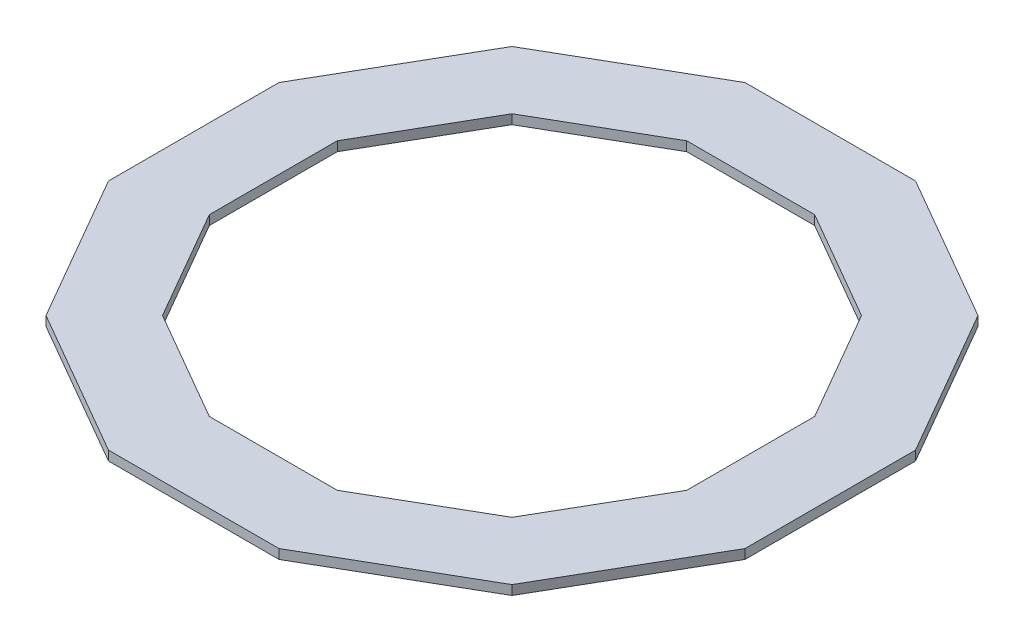
SolidWorks part; units mm, degrees
material "ABS PC"
ref_plane "Front Plane" through (0, 0, 0) normal (0, 0, 1) x (1, 0, 0)
ref_plane "Top Plane" through (0, 0, 0) normal (0, 1, 0) x (1, 0, 0)
ref_plane "Right Plane" through (0, 0, 0) normal (1, 0, 0) x (0, 0, -1)
sketch "Sketch1" plane through (0, 0, 0) normal (0, 1, 0) x (1, 0, 0)
  line L0 (26.296, 98.1381) -> (-26.296, 98.1381)
  line L1 (-26.296, 98.1381) -> (-71.842, 71.842)
  line L2 (-71.842, 71.842) -> (-98.1381, 26.296)
  line L3 (-98.1381, 26.296) -> (-98.1381, -26.296)
  line L4 (-98.1381, -26.296) -> (-71.842, -71.842)
  line L5 (-71.842, -71.842) -> (-26.296, -98.1381)
  line L6 (-26.296, -98.1381) -> (26.296, -98.1381)
  line L7 (26.296, -98.1381) -> (71.842, -71.842)
  line L8 (71.842, -71.842) -> (98.1381, -26.296)
  line L9 (98.1381, -26.296) -> (98.1381, 26.296)
  line L10 (98.1381, 26.296) -> (71.842, 71.842)
  line L11 (71.842, 71.842) -> (26.296, 98.1381)
  circle A0 centre (0, 0) radius 101.6
  dimension "D1" = 203.2
extrude "Boss-Extrude1" add sketch "Sketch1" against normal blind 2.921 contours L10 L11 L0 L1 L2 L3 L4 L5 L6 L7 L8 L9 region at (0, 0, 0)
sketch "Sketch3" plane through (0, 0, 0) normal (0, 1, 0) x (1, 0, 0)
  line L12 (-53.8815, 53.8815) -> (-19.722, 73.6035)
  line L13 (-19.722, 73.6035) -> (19.722, 73.6035)
  line L14 (19.722, 73.6035) -> (53.8815, 53.8815)
  line L15 (53.8815, 53.8815) -> (73.6035, 19.722)
  line L16 (73.6035, 19.722) -> (73.6035, -19.722)
  line L17 (73.6035, -19.722) -> (53.8815, -53.8815)
  line L18 (53.8815, -53.8815) -> (19.722, -73.6035)
  line L19 (19.722, -73.6035) -> (-19.722, -73.6035)
  line L20 (-19.722, -73.6035) -> (-53.8815, -53.8815)
  line L21 (-53.8815, -53.8815) -> (-73.6035, -19.722)
  line L22 (-73.6035, -19.722) -> (-73.6035, 19.722)
  line L23 (-73.6035, 19.722) -> (-53.8815, 53.8815)
  line L24 (-71.842, 71.842) -> (-98.1381, 26.296) construction
  line L25 (-26.296, 98.1381) -> (-71.842, 71.842) construction
  line L26 (26.296, 98.1381) -> (-26.296, 98.1381) construction
  line L27 (71.842, 71.842) -> (26.296, 98.1381) construction
  line L28 (98.1381, 26.296) -> (71.842, 71.842) construction
  line L29 (98.1381, -26.296) -> (98.1381, 26.296) construction
  line L30 (71.842, -71.842) -> (98.1381, -26.296) construction
  line L31 (26.296, -98.1381) -> (71.842, -71.842) construction
  line L32 (-26.296, -98.1381) -> (26.296, -98.1381) construction
  line L33 (-71.842, -71.842) -> (-26.296, -98.1381) construction
  line L34 (-98.1381, -26.296) -> (-71.842, -71.842) construction
  line L35 (-98.1381, 26.296) -> (-98.1381, -26.296) construction
  line L36 (-26.296, 98.1381) -> (26.296, -98.1381) construction
  line L37 (26.296, 98.1381) -> (-26.296, -98.1381) construction
  circle A0 centre (0, 0) radius 76.2
  dimension "D1" = 152.4
extrude "Cut-Extrude1" cut sketch "Sketch3" against normal through all contours L23 L22 L21 L20 L19 L18 L17 L16 L15 L14 L13 L12 region at (0, 0, 0)
